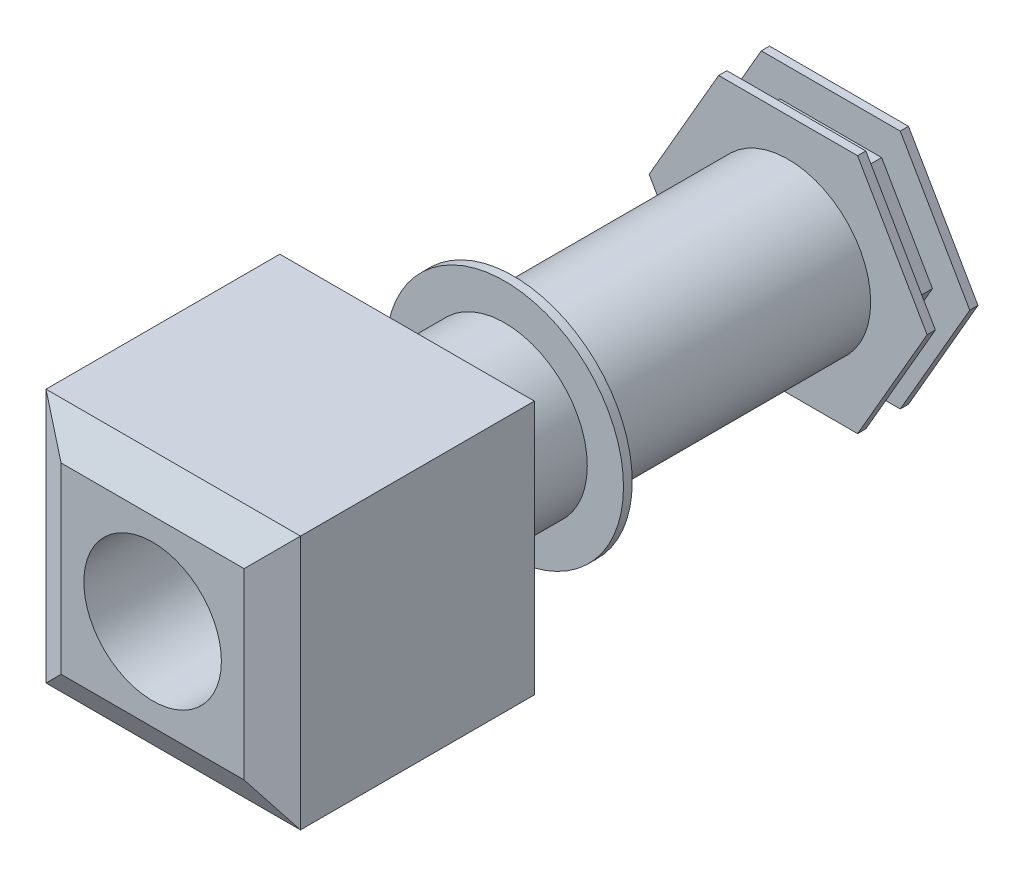
SolidWorks part; units mm, degrees
ref_plane "Front Plane" through (0, 0, 0) normal (0, 0, 1) x (1, 0, 0)
ref_plane "Top Plane" through (0, 0, 0) normal (0, 1, 0) x (1, 0, 0)
ref_plane "Right Plane" through (0, 0, 0) normal (1, 0, 0) x (0, 0, -1)
sketch "Sketch1" plane through (0, 0, 0) normal (0, 0, 1) x (1, 0, 0)
  line L1 (202.0726, 0) -> (101.0363, 175)
  line L2 (101.0363, 175) -> (-101.0363, 175)
  line L3 (-101.0363, 175) -> (-202.0726, 0)
  line L4 (-202.0726, 0) -> (-101.0363, -175)
  line L5 (-101.0363, -175) -> (101.0363, -175)
  line L6 (101.0363, -175) -> (202.0726, 0)
  circle A0 centre (0, 0) radius 175 construction
extrude "Boss-Extrude1" add sketch "Sketch1" along normal blind 12
sketch "Sketch2" plane through (0, 0, 12) normal (0, 0, 1) x (1, 0, 0)
  line L1 (147.8875, 0) -> (73.9437, 128.0743)
  line L2 (73.9437, 128.0743) -> (-73.9437, 128.0743)
  line L3 (-73.9437, 128.0743) -> (-147.8875, 0)
  line L4 (-147.8875, 0) -> (-73.9437, -128.0743)
  line L5 (-73.9437, -128.0743) -> (73.9437, -128.0743)
  line L6 (73.9437, -128.0743) -> (147.8875, 0)
  circle A0 centre (0, 0) radius 128.0743 construction
extrude "Boss-Extrude2" add sketch "Sketch2" along normal blind 50
sketch "Sketch3" plane through (0, 0, 62) normal (0, 0, 1) x (1, 0, 0)
  line L1 (202.0726, 0) -> (101.0363, 175)
  line L2 (101.0363, 175) -> (-101.0363, 175)
  line L3 (-101.0363, 175) -> (-202.0726, 0)
  line L4 (-202.0726, 0) -> (-101.0363, -175)
  line L5 (-101.0363, -175) -> (101.0363, -175)
  line L6 (101.0363, -175) -> (202.0726, 0)
  circle A0 centre (0, 0) radius 175 construction
extrude "Boss-Extrude3" add sketch "Sketch3" along normal blind 12
sketch "Sketch4" plane through (0, 0, 74) normal (0, 0, 1) x (1, 0, 0)
  circle A0 centre (0, 0) radius 120
extrude "Boss-Extrude4" add sketch "Sketch4" along normal blind 400
sketch "Sketch5" plane through (0, 0, 474) normal (0, 0, 1) x (1, 0, 0)
  circle A0 centre (0, 0) radius 172.6469
extrude "Boss-Extrude5" add sketch "Sketch5" along normal blind 12
chamfer "Chamfer1" distance 10 angle 80 1 edges at (120, 0, 474) first distance on face at (120, 0, 474)
sketch "Sketch6" plane through (0, 0, 486) normal (0, 0, 1) x (1, 0, 0)
  circle A0 centre (0, 0) radius 120
extrude "Boss-Extrude6" add sketch "Sketch6" along normal blind 130
sketch "Sketch8" plane through (0, 0, 616) normal (0, 0, 1) x (1, 0, 0)
  circle A0 centre (0, 0) radius 172.6469
extrude "Boss-Extrude7" add sketch "Sketch8" along normal blind 12
chamfer "Chamfer2" distance 6 angle 70 1 edges at (120, 0, 616) first distance on face at (120, 0, 616)
sketch "Sketch9" plane through (0, 0, 628) normal (0, 0, 1) x (1, 0, 0)
  line L1 (-185, 185) -> (185, 185)
  line L2 (-185, 185) -> (-185, -185)
  line L3 (-185, -185) -> (185, -185)
  line L4 (185, 185) -> (185, -185)
  line L5 (-185, 185) -> (185, -185) construction
  line L6 (-185, -185) -> (185, 185) construction
  point P0 (0, 0)
extrude "Boss-Extrude8" add sketch "Sketch9" along normal blind 370
sketch "Sketch10" plane through (0, 0, 998) normal (0, 0, 1) x (1, 0, 0)
  circle A0 centre (0, 0) radius 100
extrude "Cut-Extrude1" cut sketch "Sketch10" against normal blind 900
chamfer "Chamfer3" distance 30 angle 60 4 edges at (185, 0, 998) (0, -185, 998) (-185, 0, 998) (0, 185, 998) first distance on face at (185, 0, 813) first distance on face at (0, -185, 813) first distance on face at (-185, 0, 813) first distance on face at (0, 185, 813)
